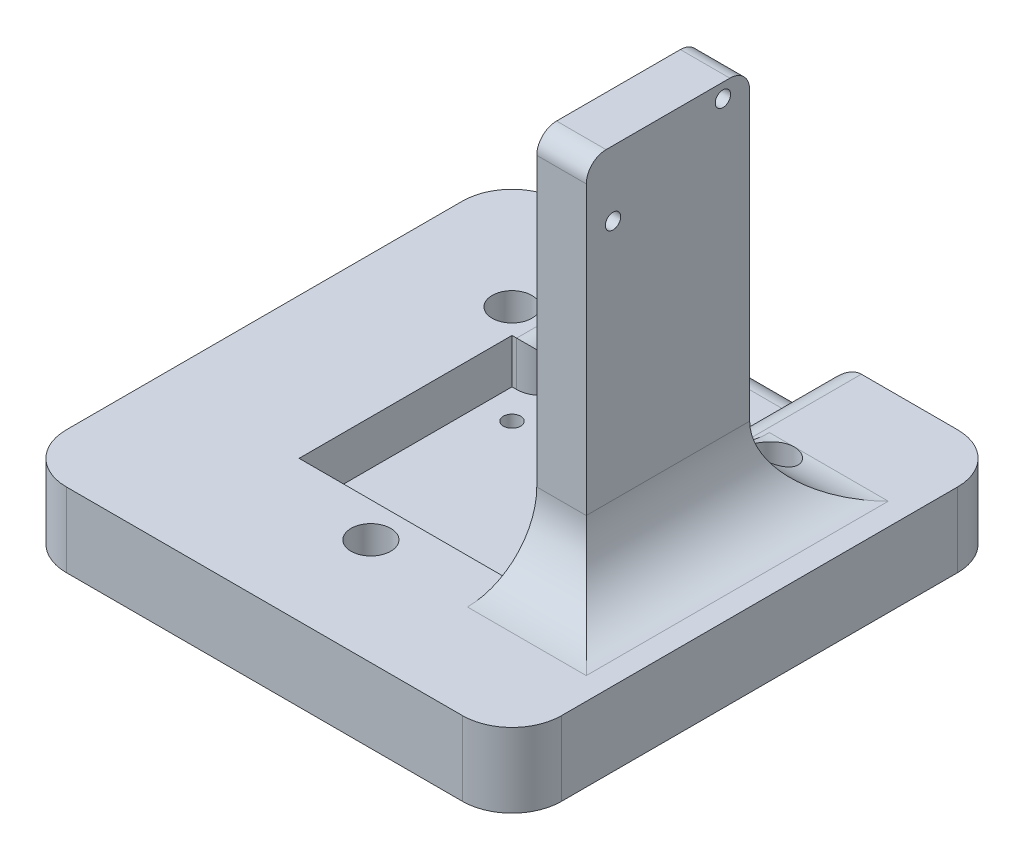
SolidWorks part; units mm, degrees
ref_plane "Front Plane" through (0, 0, 0) normal (0, 0, 1) x (1, 0, 0)
ref_plane "Top Plane" through (0, 0, 0) normal (0, 1, 0) x (1, 0, 0)
ref_plane "Right Plane" through (0, 0, 0) normal (1, 0, 0) x (0, 0, -1)
sketch "Sketch1" plane through (0, 0, 0) normal (0, 1, 0) x (1, 0, 0)
  line L1 (-50, -50) -> (50, -50)
  line L2 (-50, -50) -> (-50, 50)
  line L3 (-50, 50) -> (50, 50)
  line L4 (50, -50) -> (50, 50)
  line L5 (-50, -50) -> (50, 50) construction
  line L6 (-50, 50) -> (50, -50) construction
  point P0 (0, 0)
  dimension "D1" = 100
  dimension "D2" = 100
extrude "Boss-Extrude1" add sketch "Sketch1" along normal blind 15
sketch "Sketch2" plane through (0, 15, 0) normal (0, 1, 0) x (1, 0, 0)
  line L1 (-21.5, -21.5) -> (21.5, -21.5)
  line L2 (-21.5, -21.5) -> (-21.5, 21.5)
  line L3 (-21.5, 21.5) -> (21.5, 21.5)
  line L4 (21.5, -21.5) -> (21.5, 21.5)
  line L5 (-21.5, -21.5) -> (21.5, 21.5) construction
  line L6 (-21.5, 21.5) -> (21.5, -21.5) construction
  circle A0 centre (-26.5, 26.5) radius 4.01
  circle A1 centre (0, -28.5) radius 4.01
  circle A2 centre (26.5, 26.5) radius 4.01
  point P0 (0, 0)
  point P14 (0, -21.5)
  dimension "D3" = 8.02
  dimension "D7" = 5
  dimension "D1" = 43
  dimension "D2" = 43
  dimension "D4" = 7
  dimension "D5" = 5
  dimension "D6" = 5
extrude "Cut-Extrude1" cut sketch "Sketch2" against normal offset from surface (9 mm away) 6 up to face at (0, 0, 0)
sketch "Sketch3" plane through (0, 0, -50) normal (0, 0, -1) x (-1, 0, 0)
  line L0 (-50, 15) -> (50, 15) construction
  line L1 (-15.5633, 15) -> (15.5633, 15)
  line L2 (-15.5633, 15) -> (-15.5633, 6)
  line L3 (-15.5633, 6) -> (15.5633, 6)
  line L4 (15.5633, 15) -> (15.5633, 6)
  line L6 (-15.5633, 14.5) -> (-15.5633, 37) construction
  line L7 (15.5633, 37) -> (15.5633, 14.5) construction
  line L8 (-21.5, 6) -> (21.5, 6) construction
  dimension "D1" = 0
extrude "Cut-Extrude2" cut sketch "Sketch3" against normal up to surface (28.5 mm away) up to face at (0, 10.5, -21.5)
sketch "Sketch4" plane through (0, 0, 0) normal (0, -1, 0) x (1, 0, 0)
  circle A0 centre (-15.5, 15.5) radius 1.75
  circle A1 centre (15.5, 15.5) radius 1.75
  circle A2 centre (15.5, -15.5) radius 1.75
  circle A3 centre (-15.5, -15.5) radius 1.75
  dimension "D1" = 3.5
extrude "Cut-Extrude3" cut sketch "Sketch4" against normal up to surface (6 mm away) up to face at (0, 6, -17.875)
sketch "Sketch5" plane through (0, 0, 0) normal (0, -1, 0) x (1, 0, 0)
  circle A18 centre (-15.5, 15.5) radius 3.75
  circle A19 centre (-15.5, 15.5) radius 3.75
  circle A21 centre (15.5, 15.5) radius 3.75
  circle A22 centre (15.5, 15.5) radius 3.75
  circle A24 centre (-15.5, -15.5) radius 3.75
  circle A25 centre (-15.5, -15.5) radius 3.75
  circle A27 centre (15.5, -15.5) radius 3.75
  circle A28 centre (15.5, -15.5) radius 3.75
  dimension "D1" = 2
  dimension "D2" = 2
  dimension "D3" = 2
  dimension "D4" = 2
extrude "Cut-Extrude4" cut sketch "Sketch5" against normal blind 3
fillet "Fillet1" radius 10 4 edges at (-50, 7.5, 50) (-50, 7.5, -50) (50, 7.5, -50) (50, 7.5, 50)
fillet "Fillet2" radius 5 7 edges at (-15.5633, 10.5, -21.5) (-15.5633, 10.5, -50) (-15.5633, 15, -35.75) (15.5633, 10.5, -50) (15.5633, 15, -35.75) (15.5633, 10.5, -21.5) (0, 6, -50)
sketch "Sketch6" plane through (0, 15, 0) normal (0, 1, 0) x (1, 0, 0)
  line L0 (21.5, -21.5) -> (21.5, 21.5) construction
  line L1 (21.5, -16.5) -> (31.5, -16.5)
  line L2 (21.5, -16.5) -> (21.5, 16.5)
  line L3 (21.5, 16.5) -> (31.5, 16.5)
  line L4 (31.5, -16.5) -> (31.5, 16.5)
  line L5 (-21.5, -21.5) -> (21.5, -21.5) construction
  line L6 (21.5, 21.5) -> (20.5633, 21.5) construction
  dimension "D1" = 5
  dimension "D2" = 5
  dimension "D3" = 10
extrude "Boss-Extrude2" add sketch "Sketch6" along normal blind 76
sketch "Sketch7" plane through (31.5, 0, 0) normal (1, 0, 0) x (0, 0, -1)
  circle A0 centre (11.1, 88.1) radius 1.55
  circle A1 centre (-11.1, 77.8) radius 1.55
  dimension "D1" = 3.1
extrude "Cut-Extrude5" cut sketch "Sketch7" against normal through all both and the other way through all
fillet "Fillet3" radius 4 2 edges at (26.5, 91, -16.5) (26.5, 91, 16.5)
fillet "Fillet4" radius 14 3 edges at (26.5, 15, -16.5) (26.5, 15, 16.5) (31.5, 15, 0)
